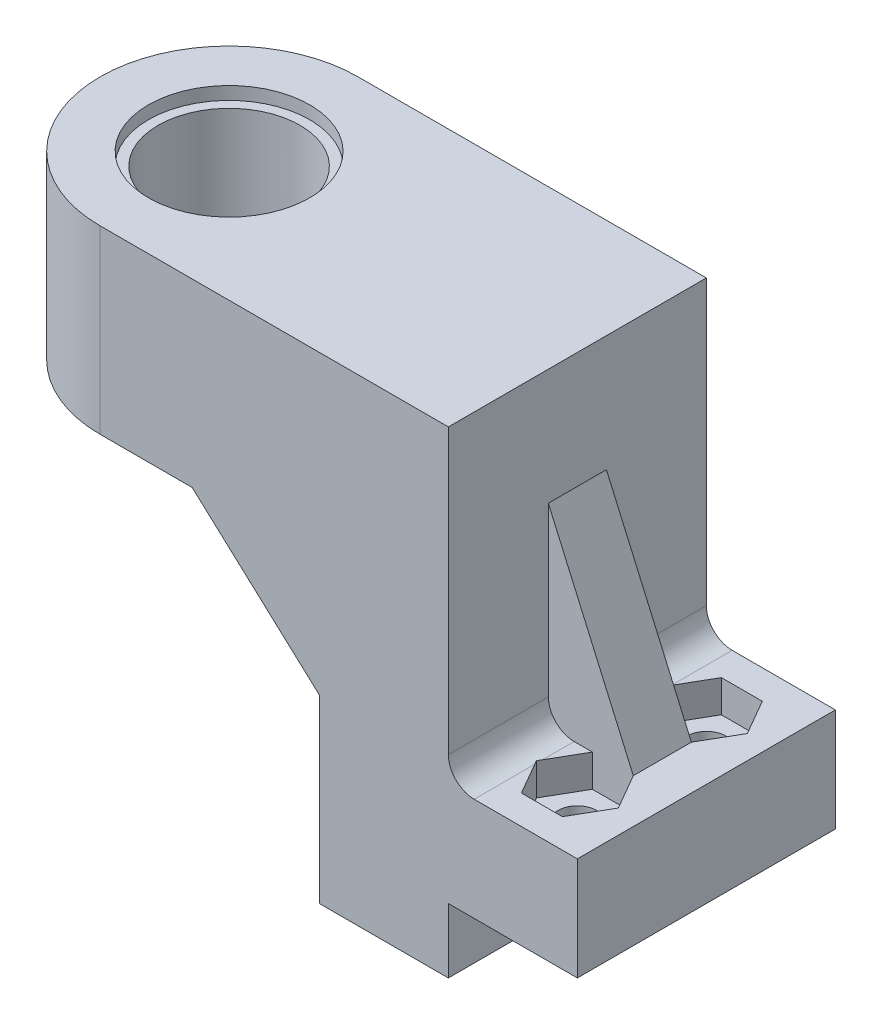
SolidWorks part; units mm, degrees
material "ABS"
ref_plane "前视基准面" through (0, 0, 0) normal (0, 0, 1) x (1, 0, 0)
ref_plane "上视基准面" through (0, 0, 0) normal (0, 1, 0) x (1, 0, 0)
ref_plane "右视基准面" through (0, 0, 0) normal (1, 0, 0) x (0, 0, -1)
sketch "草图1" plane through (0, 0, 0) normal (0, 0, 1) x (1, 0, 0)
  line L0 (-63.8668, 22.9477) -> (-23.8668, 22.9477)
  line L1 (-23.8668, 22.9477) -> (-23.8668, -19.0523)
  line L4 (-23.8668, -19.0523) -> (-33.8668, -19.0523)
  line L5 (-33.8668, -19.0523) -> (-33.8668, 14.9477)
  line L6 (-33.8668, 14.9477) -> (-63.8668, 14.9477)
  line L7 (-63.8668, 14.9477) -> (-63.8668, 22.9477)
  dimension "D2" = 42
  dimension "D3" = 10
  dimension "D5" = 8
  dimension "D6" = 30
extrude "凸台-拉伸1" add sketch "草图1" along normal blind 20
sketch "草图3" plane through (0, 22.9477, 0) normal (0, 1, 0) x (-1, 0, 0)
  line L0 (23.8668, 0) -> (63.8668, 0) construction
  line L1 (33.8668, 20) -> (33.8668, 0) construction
  circle A0 centre (50.8668, 10) radius 5.5
  dimension "D3" = 11
  dimension "D1" = 10
  dimension "D2" = 17
extrude "切除-拉伸2" cut sketch "草图3" against normal blind 10
sketch3d "3D草图2" plane through (0, 0, 0) normal (0, 0, 1) x (1, 0, 0)
sketch "草图9" plane through (0, 22.9477, 0) normal (0, 1, 0) x (1, 0, 0)
  circle A0 centre (-50.8668, -10) radius 6.25
  dimension "D1" = 12.5
extrude "切除-拉伸6" cut sketch "草图9" against normal blind 1
sketch "草图11" plane through (-23.8668, 0, 0) normal (1, 0, 0) x (0, 0, -1)
  line L0 (0, -19.0523) -> (0, 22.9477) construction
  line L1 (-20, -19.0523) -> (0, -19.0523)
  line L2 (-20, -19.0523) -> (-20, -14.0523)
  line L3 (-20, -14.0523) -> (0, -14.0523)
  line L4 (0, -19.0523) -> (0, -14.0523)
  dimension "D1" = 5
extrude "凸台-拉伸4" add sketch "草图11" along normal blind 10
sketch "草图12" plane through (0, -14.0523, 0) normal (0, 1, 0) x (-1, 0, 0)
  line L0 (13.8668, 0) -> (23.8668, 0) construction
  line L1 (13.8668, 20) -> (23.8668, 20) construction
  line L2 (13.8668, 0) -> (13.8668, 20) construction
  circle A0 centre (18.8668, 5) radius 1.5
  circle A1 centre (18.8668, 15) radius 1.5
  dimension "D1" = 3
  dimension "D4" = 5
  dimension "D5" = 5
  dimension "D2" = 5
  dimension "D3" = 5
extrude "切除-拉伸8" cut sketch "草图12" against normal up to next
sketch "草图13" plane through (0, -19.0523, 0) normal (0, -1, 0) x (1, 0, 0)
  circle A0 centre (-18.8668, 15) radius 3
  circle A1 centre (-18.8668, 5) radius 3
  dimension "D1" = 6
  dimension "D2" = 6
extrude "切除-拉伸9" cut sketch "草图13" against normal blind 2.5
sketch "草图14" plane through (0, 14.9477, 0) normal (0, -1, 0) x (1, 0, 0)
  circle A0 centre (-50.8668, 10) radius 10
  circle A1 centre (-50.8668, 10) radius 5.5
  dimension "D1" = 11
  dimension "D2" = 20
extrude "凸台-拉伸5" add sketch "草图14" along normal blind 6
sketch "草图6" plane through (0, 8.9477, 0) normal (0, -1, 0) x (1, 0, 0)
  circle A0 centre (-50.8668, 10) radius 6.25
  dimension "D1" = 12.5
extrude "切除-拉伸10" cut sketch "草图6" against normal blind 1
sketch "草图15" plane through (-13.8668, 0, 0) normal (1, 0, 0) x (0, 0, -1)
  line L1 (0, -19.0523) -> (-20, -19.0523)
  line L2 (0, -19.0523) -> (0, -14.0523)
  line L3 (0, -14.0523) -> (-20, -14.0523)
  line L4 (-20, -19.0523) -> (-20, -14.0523)
extrude "凸台-拉伸6" add sketch "草图15" along normal blind 5
sketch "草图16" plane through (0, 14.9477, 0) normal (0, -1, 0) x (1, 0, 0)
  line L1 (-33.8668, 20) -> (-50.8668, 20)
  line L2 (-33.8668, 20) -> (-33.8668, 17)
  line L3 (-33.8668, 17) -> (-50.8668, 17)
  line L4 (-50.8668, 20) -> (-50.8668, 17)
  line L5 (-33.8668, 0) -> (-50.8668, 0)
  line L6 (-33.8668, 0) -> (-33.8668, 3)
  line L7 (-33.8668, 3) -> (-50.8668, 3)
  line L8 (-50.8668, 0) -> (-50.8668, 3)
  dimension "D1" = 3
  dimension "D2" = 3
extrude "凸台-拉伸7" add sketch "草图16" along normal blind 15
sketch "草图17" plane through (0, 0, 17) normal (0, 0, -1) x (-1, 0, 0)
  line L0 (50.8668, 8.9477) -> (43.7254, 8.9477)
  line L1 (43.7254, 8.9477) -> (33.8668, -0.0523)
  line L2 (33.8668, -0.0523) -> (50.8668, -0.0523)
  line L3 (50.8668, -0.0523) -> (50.8668, 8.9477)
extrude "切除-拉伸11" cut sketch "草图17" against normal through all and the other way through all
sketch3d "3D草图3"
  line L0 (-23.8668, -14.0523, 20) -> (-23.8668, 22.9477, 20) construction
  line L1 (-23.8668, -6.0523, 20) -> (-13.8668, -6.0523, 20)
  line L2 (-23.8668, -6.0523, 20) -> (-23.8668, -6.0523, 0)
  line L3 (-23.8668, -6.0523, 0) -> (-13.8668, -6.0523, 0)
  line L4 (-13.8668, -6.0523, 20) -> (-13.8668, -6.0523, 0)
  circle A0 centre (-18.8668, -6.0523, 15) radius 1.5
  circle A1 centre (-18.8668, -6.0523, 5) radius 1.5
  point P8 (-18.8668, -4.5523, 15)
  point P11 (-18.8668, -4.5523, 5)
  dimension "D4" = 3
  dimension "D5" = 3
  dimension "D6" = 5
  dimension "D7" = 5
  dimension "D8" = 5
  dimension "D9" = 5
  dimension "D1" = 8
  dimension "D2" = 10
  dimension "D3" = 20
extrude "凸台-拉伸8" add sketch "3D草图3" along a picked direction on the side against the normal blind 5
sketch "草图18" plane through (0, -1.0523, 0) normal (0, 1, 0) x (-1, 0, 0)
  line L1 (15.6914, 15) -> (17.2791, 12.25)
  line L2 (17.2791, 12.25) -> (20.4545, 12.25)
  line L3 (20.4545, 12.25) -> (22.0422, 15)
  line L4 (22.0422, 15) -> (20.4545, 17.75)
  line L5 (20.4545, 17.75) -> (17.2791, 17.75)
  line L6 (17.2791, 17.75) -> (15.6914, 15)
  line L7 (15.6914, 5) -> (17.2791, 2.25)
  line L8 (17.2791, 2.25) -> (20.4545, 2.25)
  line L9 (20.4545, 2.25) -> (22.0422, 5)
  line L10 (22.0422, 5) -> (20.4545, 7.75)
  line L11 (20.4545, 7.75) -> (17.2791, 7.75)
  line L12 (17.2791, 7.75) -> (15.6914, 5)
  circle A0 centre (18.8668, 15) radius 2.75 construction
  circle A1 centre (18.8668, 5) radius 2.75 construction
  dimension "D1" = 5.5
  dimension "D2" = 5.5
extrude "切除-拉伸12" cut sketch "草图18" against normal blind 2.5
fillet "圆角1" radius 2 1 edges
sketch "草图19" plane through (0, 22.9477, 0) normal (0, 1, 0) x (1, 0, 0)
  line L0 (-23.8668, -17) -> (-31.8668, -17)
  line L1 (-23.8668, -20) -> (-23.8668, 0) construction
  line L2 (-31.8668, -17) -> (-31.8668, -20)
  line L3 (-23.8668, -20) -> (-63.8668, -20) construction
  line L4 (-31.8668, -20) -> (-23.8668, -20)
  line L5 (-23.8668, -20) -> (-23.8668, -17)
  dimension "D1" = 8
  dimension "D2" = 3
extrude "切除-拉伸13" [suppressed] cut sketch "草图19" against normal blind 13
sketch "草图20" plane through (0, 14.9477, 0) normal (0, -1, 0) x (1, 0, 0)
  line L0 (-63.8668, 20) -> (-50.8668, 20)
  line L2 (-50.8668, 0) -> (-63.8668, 0)
  line L3 (-63.8668, 0) -> (-63.8668, 20)
  arc A0 (-50.8668, 20) -> (-50.8668, 0) centre (-50.8668, 10) ccw
extrude "切除-拉伸14" cut sketch "草图20" against normal through all
sketch "草图21" plane through (0, -1.0523, 0) normal (0, 1, 0) x (1, 0, 0)
  line L0 (-17.2791, -7.75) -> (-23.8668, -7.75)
  line L1 (-23.8668, -20) -> (-23.8668, 0) construction
  line L2 (-23.8668, -7.75) -> (-23.8668, -12.25)
  line L3 (-23.8668, -12.25) -> (-17.2791, -12.25)
  line L4 (-17.2791, -12.25) -> (-17.2791, -7.75)
extrude "凸台-拉伸9" add sketch "草图21" along normal blind 15
sketch "草图22" [suppressed] plane through (0, 0, 12.25) normal (0, 0, 1) x (1, 0, 0)
  line L0 (-17.2791, 13.9477) -> (-23.8668, 13.9477)
  line L1 (-23.8668, 9.9477) -> (-23.8668, 22.9477) construction
  line L2 (-23.8668, 13.9477) -> (-17.2791, -1.0523)
  line L3 (-17.2791, -1.0523) -> (-17.2791, 13.9477)
extrude "切除-拉伸15" [suppressed] cut sketch "草图22" against normal up to next
fillet "圆角3" [suppressed] radius 2
sketch "草图23" plane through (0, -19.0523, 0) normal (0, -1, 0) x (1, 0, 0)
  line L1 (-33.8668, 0) -> (-8.8668, 0)
  line L2 (-33.8668, 0) -> (-33.8668, 20)
  line L3 (-33.8668, 20) -> (-8.8668, 20)
  line L4 (-8.8668, 0) -> (-8.8668, 20)
extrude "切除-拉伸16" cut sketch "草图23" against normal up to surface (5 mm away) up to face at (-20.3668, -14.0523, 15)
sketch "草图24" plane through (0, 0, 12.25) normal (0, 0, 1) x (1, 0, 0)
  line L0 (-23.8668, 13.9477) -> (-17.2791, -1.0523)
  line L1 (-17.2791, -1.0523) -> (-17.2791, 13.9477)
  line L2 (-17.2791, 13.9477) -> (-23.8668, 13.9477)
extrude "切除-拉伸17" cut sketch "草图24" against normal blind 10
sketch "草图25" plane through (0, -6.0523, 0) normal (0, -1, 0) x (1, 0, 0)
  line L1 (-13.8668, 20) -> (-23.8668, 20)
  line L2 (-13.8668, 20) -> (-13.8668, 0)
  line L3 (-13.8668, 0) -> (-23.8668, 0)
  line L4 (-23.8668, 20) -> (-23.8668, 0)
extrude "凸台-拉伸10" add sketch "草图25" along normal blind 3
sketch "草图26" plane through (0, -6.0523, 0) normal (0, 1, 0) x (1, 0, 0)
  circle A0 centre (-18.8668, -15) radius 1.5
extrude "切除-拉伸18" cut sketch "草图26" against normal through all
sketch "草图27" plane through (0, -6.0523, 0) normal (0, 1, 0) x (1, 0, 0)
  circle A0 centre (-18.8668, -5) radius 1.5
extrude "切除-拉伸19" cut sketch "草图27" against normal through all
